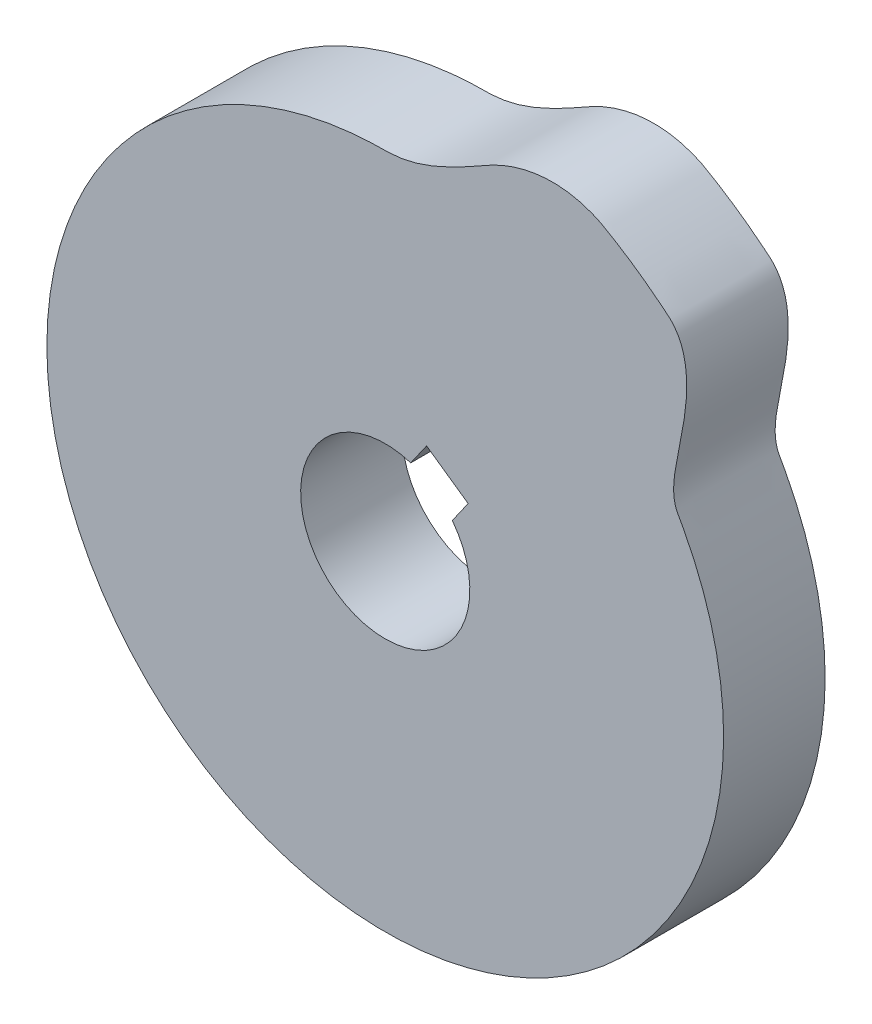
SolidWorks part; units mm, degrees
material "45"
ref_plane "前视基准面" through (0, 0, 0) normal (0, 0, 1) x (1, 0, 0)
ref_plane "上视基准面" through (0, 0, 0) normal (0, 1, 0) x (1, 0, 0)
ref_plane "右视基准面" through (0, 0, 0) normal (1, 0, 0) x (0, 0, -1)
ref_axis "基准轴1" through (0, 0, -88.99) along (0, 0, 1)
sketch "草图1" plane through (0, 0, 0) normal (0, 0, 1) x (1, 0, 0)
  arc A0 (26, 45.0333) -> (33.425, 39.8343) centre (0, 0) cw construction
  arc A1 (34.641, 20) -> (0, 40) centre (0, 0) cw construction
  spline S0 degree 3 poles (0, 40) (0.4677, 39.9999) (1.1731, 40.0423) (2.1119, 40.1793) (2.8276, 40.3235) (3.5533, 40.5084) (4.2917, 40.7332) (5.0452, 40.9976) (5.8165, 41.3008) (6.608, 41.6421) (7.4222, 42.0207) (8.2616, 42.4358) (9.1288, 42.8862) (10.0257, 43.3715) (10.9564, 43.8879) (11.9061, 44.4383) (12.8788, 44.969) (13.8739, 45.4249) (14.8711, 45.811) (15.869, 46.125) (16.8641, 46.3679) (17.8534, 46.5401) (18.8339, 46.6421) (19.8026, 46.6749) (20.7564, 46.6391) (21.6925, 46.5357) (22.608, 46.3657) (23.4998, 46.1302) (24.6514, 45.7313) (25.4752, 45.3364) (26, 45.0333) knots 0 0 0 0 0.050769 0.076601 0.102959 0.130005 0.157886 0.18674 0.21669 0.247849 0.280315 0.314179 0.349519 0.386408 0.424908 0.465077 0.505598 0.545165 0.583829 0.621645 0.658671 0.694967 0.730596 0.765623 0.800118 0.83415 0.867793 0.901122 0.934214 1 1 1 1 construction
  spline S1 degree 3 poles (33.425, 39.8343) (33.8976, 39.44) (34.4965, 38.702) (35.0457, 37.545) (35.3509, 36.5685) (35.5473, 35.5115) (35.6428, 34.389) (35.6471, 33.217) (35.5724, 32.0121) (35.4328, 30.7912) (35.2442, 29.5708) (35.0241, 28.3667) (34.7909, 27.1935) (34.5634, 26.0641) (34.3605, 24.9895) (34.2006, 23.9783) (34.1012, 23.0361) (34.0789, 22.1661) (34.1689, 21.1346) (34.3983, 20.4162) (34.641, 20) knots 0 0 0 0 0.089154 0.136079 0.185414 0.237407 0.292005 0.348896 0.407561 0.467325 0.527409 0.586977 0.645185 0.701226 0.754382 0.804082 0.849964 0.891955 0.930365 1 1 1 1 construction
  spline S2 degree 3 poles (27.3518, 44.2253) (29.3939, 42.9624) (31.3437, 41.5612) (33.192, 40.0286) (33.2219, 40.0038) (33.2817, 39.9541) (33.3712, 39.8794) (33.4308, 39.8295) (33.4605, 39.8045) (33.483, 39.7855) (33.5281, 39.7476) (33.593, 39.6877) (33.636, 39.6475) (33.6574, 39.6273) (34.0276, 39.2755) (34.5411, 38.6081) (35.0457, 37.545) (35.3509, 36.5685) (35.5473, 35.5115) (35.6428, 34.389) (35.6471, 33.217) (35.5724, 32.0121) (35.4328, 30.7912) (35.2442, 29.5708) (35.0241, 28.3667) (34.7909, 27.1935) (34.5634, 26.0641) (34.3605, 24.9895) (34.2006, 23.9783) (34.1012, 23.0361) (34.0789, 22.1661) (34.1609, 21.226) (34.3443, 20.5934) (34.5122, 20.2432) (34.5393, 20.1867) (34.5966, 20.075) (34.6916, 19.9124) (34.7538, 19.8034) (34.7848, 19.7489) (59.3505, -23.5199) (24.4432, -58.9762) (-19.2037, -35.0887) (-62.8506, -11.2012) (-51.8019, 37.3126) (-2.1155, 39.944) (-1.6609, 39.9681) (-0.7511, 40.0007) (0.6198, 39.9896) (1.5258, 40.0896) (1.975, 40.1628) (2.0187, 40.1699) (2.3018, 40.2176) (2.8276, 40.3235) (3.5533, 40.5084) (4.2917, 40.7332) (5.0452, 40.9976) (5.8165, 41.3008) (6.608, 41.6421) (7.4222, 42.0207) (8.2616, 42.4358) (9.1288, 42.8862) (10.0257, 43.3715) (10.9564, 43.8879) (11.9061, 44.4383) (12.8788, 44.969) (13.8739, 45.4249) (14.8711, 45.811) (15.869, 46.125) (16.8641, 46.3679) (17.8534, 46.5401) (18.8339, 46.6421) (19.8026, 46.6749) (20.7564, 46.6391) (21.6925, 46.5357) (22.608, 46.3657) (23.4998, 46.1302) (24.1486, 45.9054) (24.5006, 45.7645) (24.5693, 45.7363) (24.7225, 45.6733) (25.0263, 45.541) (25.4787, 45.3312) (25.7667, 45.1675) (25.9103, 45.085) (26.072, 44.9921) (26.3943, 44.8045) (26.8749, 44.5179) (27.1932, 44.3234) (27.3518, 44.2253) (29.3939, 42.9624) (31.3437, 41.5612) knots -0.002618 0 0 0 0.033656 0.033656 0.033656 0.034201 0.034747 0.035292 0.035292 0.035292 0.035706 0.036119 0.036532 0.036532 0.036532 0.043702 0.048243 0.053016 0.058047 0.06333 0.068834 0.07451 0.080293 0.086107 0.09187 0.097502 0.102924 0.108068 0.112876 0.117316 0.121379 0.125095 0.130547 0.130547 0.130547 0.131427 0.132308 0.133188 0.133188 0.133188 0.493312 0.493312 0.493312 0.853435 0.853435 0.853435 0.859825 0.866215 0.872605 0.872605 0.872605 0.873227 0.876635 0.880133 0.883738 0.887469 0.891342 0.895371 0.89957 0.903949 0.908519 0.913289 0.918268 0.923462 0.928702 0.933819 0.938818 0.943709 0.948497 0.95319 0.957798 0.962327 0.966788 0.971189 0.975539 0.979849 0.984128 0.985171 0.985171 0.985171 0.987496 0.989821 0.992147 0.992147 0.992147 0.994764 0.997382 1 1 1 1.033656 1.033656 1.033656 weights 1 0.998404 0.998404 1 1 1 1 1 1 1 1 1 1 1 1 1 1 1 1 1 1 1 1 1 1 1 1 1 1 1 1 1 1 1 1 1 1 1 1 0.515542 0.515542 1 0.515542 0.515542 1 1 1 1 1 1 1 1 1 1 1 1 1 1 1 1 1 1 1 1 1 1 1 1 1 1 1 1 1 1 1 1 1 1 1 1 1 1 1 1 1 1 1 1 1 0.998404 0.998404 only from (27.3518, 44.2253) to (27.3518, 44.2253)
extrude "凸台-拉伸1" add sketch "草图1" along normal blind 12
sketch "草图2" plane through (0, 0, 0) normal (0, 0, 1) x (1, 0, 0)
  line L0 (3.0141, 9.5349) -> (4.8843, 12.2059)
  line L1 (4.8843, 12.2059) -> (9.7992, 8.7644)
  line L2 (9.7992, 8.7644) -> (7.929, 6.0935)
  arc A0 (3.0141, 9.5349) -> (7.929, 6.0935) centre (0, 0) ccw
extrude "切除-拉伸1" cut sketch "草图2" against normal blind 12 and the other way blind 12
